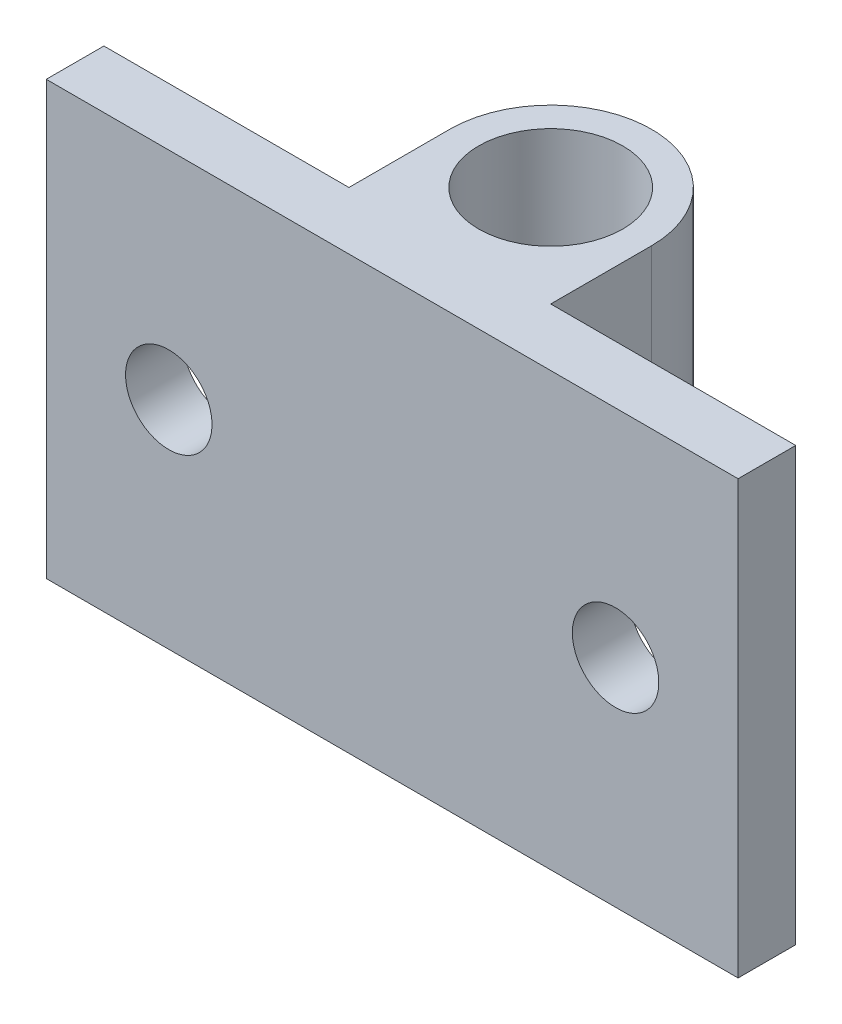
SolidWorks part; units mm, degrees
ref_plane "Front" through (0, 0, 0) normal (0, 0, 1) x (1, 0, 0)
ref_plane "Top" through (0, 0, 0) normal (0, 1, 0) x (1, 0, 0)
ref_plane "Right" through (0, 0, 0) normal (1, 0, 0) x (0, 0, -1)
sketch "Sketch1" plane through (0, 0, 0) normal (0, 1, 0) x (1, 0, 0)
  line L0 (0, 0) -> (0, -5.5)
  line L1 (0, -5.5) -> (12, -5.5)
  line L2 (0, -5.5) -> (-12, -5.5)
  line L3 (-12, -5.5) -> (-12, -3.5)
  line L4 (0, 2.5) -> (0, 3.5)
  line L5 (-2.5, 0) -> (-3.5, 0)
  line L6 (2.5, 0) -> (3.5, 0)
  line L7 (-3.5, 0) -> (-3.5, -3.5)
  line L8 (-3.5, -3.5) -> (-12, -3.5)
  line L9 (3.5, 0) -> (3.5, -3.5)
  line L10 (12, -5.5) -> (12, -3.5)
  line L11 (12, -3.5) -> (3.5, -3.5)
  circle A0 centre (0, 0) radius 2.5
  arc A1 (-3.5, 0) -> (3.5, 0) centre (0, 0) cw
  dimension "D1" = 12
  dimension "D3" = 5.5
  dimension "D4" = 2
  dimension "D2" = 12
  dimension "D5" = 1
  dimension "D6" = 1
  dimension "D7" = 1
extrude "Boss-Extrude1" add sketch "Sketch1" along normal blind 15 contours A1 L4 A0 L6 | A1 L5 A0 L4 | A0 L5 L7 L8 L3 L2 L0 | A0 L0 L1 L10 L11 L9 L6 region at (5.1124, 0, 3.9638) region at (-5.1124, 0, 3.9638) region at (-1.9275, 0, -1.9275) region at (1.9275, 0, -1.9275)
sketch "Sketch2" plane through (0, 0, 3.5) normal (0, 0, -1) x (-1, 0, 0)
  line L0 (7.75, 15) -> (7.75, 0)
  line L1 (3.5, 15) -> (12, 15) construction
  line L2 (3.5, 0) -> (12, 0) construction
  line L3 (-7.75, 15) -> (-7.75, 0)
  line L4 (-12, 15) -> (-3.5, 15) construction
  line L5 (-12, 0) -> (-3.5, 0) construction
  circle A0 centre (7.75, 7.5) radius 1.5
  circle A1 centre (-7.75, 7.5) radius 1.5
extrude "Cut-Extrude1" cut sketch "Sketch2" against normal through all contours L3 A1 | L3 A1 | L0 A0 | L0 A0 region at (-8.3866, 7.5, 3.5) region at (-7.1134, 7.5, 3.5) region at (7.1134, 7.5, 3.5) region at (8.3866, 7.5, 3.5)
sketch "Sketch3" plane through (0, 0, 3.5) normal (0, 0, -1) x (-1, 0, 0)
  line L0 (3.5, 0) -> (3.5, 7.5)
  line L1 (3.5, 15) -> (3.5, 0) construction
  line L2 (3.5, 7.5) -> (-3.5, 7.5)
  line L3 (-3.5, 15) -> (-3.5, 0) construction
  line L4 (-3.5, 7.5) -> (-3.5, 0)
  line L5 (-3.5, 0) -> (3.5, 0)
extrude "Cut-Extrude2" cut sketch "Sketch3" along normal through all
